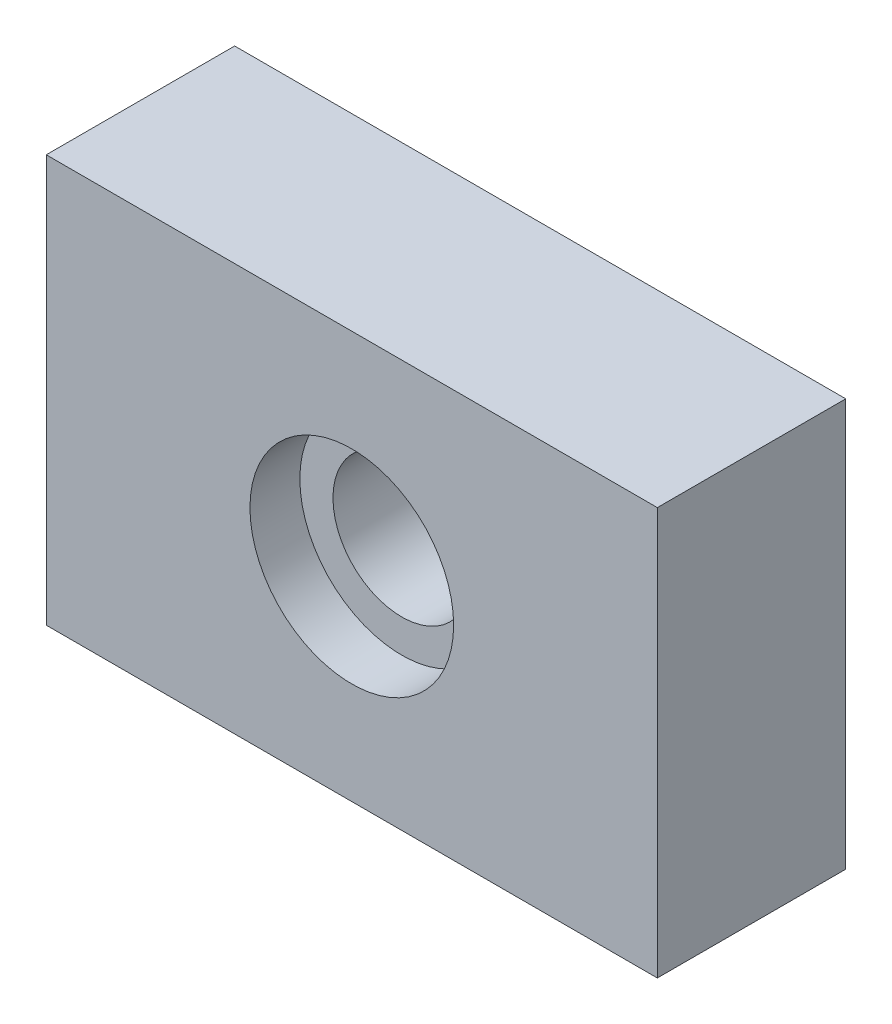
SolidWorks part; units mm, degrees
material "1060 Alloy"
ref_plane "Front Plane" through (0, 0, 0) normal (0, 0, 1) x (1, 0, 0)
ref_plane "Top Plane" through (0, 0, 0) normal (0, 1, 0) x (1, 0, 0)
ref_plane "Right Plane" through (0, 0, 0) normal (1, 0, 0) x (0, 0, -1)
sketch "Sketch1" plane through (0, 0, 0) normal (0, 0, 1) x (1, 0, 0)
  line L1 (0, 0) -> (152.4, 0)
  line L2 (0, 0) -> (0, 101.6)
  line L3 (0, 101.6) -> (152.4, 101.6)
  line L4 (152.4, 0) -> (152.4, 101.6)
  dimension "D1" = 152.4
  dimension "D2" = 101.6
extrude "Boss-Extrude1" add sketch "Sketch1" along normal blind 46.99
sketch "Sketch2" plane through (0, 0, 0) normal (0, 0, -1) x (-1, 0, 0)
  line L0 (0, 50.8) -> (-152.4, 50.8) construction
  line L1 (0, 101.6) -> (0, 0) construction
  line L2 (-152.4, 0) -> (-152.4, 101.6) construction
  line L4 (-152.4, 101.6) -> (0, 101.6) construction
  line L5 (-76.2, 101.6) -> (-76.2, 0) construction
  line L6 (0, 0) -> (-152.4, 0) construction
  circle A0 centre (-76.2, 50.8) radius 25.4
  circle A1 centre (-76.2, 50.8) radius 17.145
  dimension "D1" = 50.8
  dimension "D2" = 34.29
extrude "Cut-Extrude1" cut sketch "Sketch2" against normal through all contours A1
extrude "Cut-Extrude3" cut sketch "Sketch2<2>" against normal blind 12.446
sketch "Sketch2<2>" plane through (0, 0, 0) normal (0, 0, -1) x (-1, 0, 0) same geometry as "Sketch2"
ref_plane "Plane2" through (0, 0, 23.495) normal (0, 0, -1) x (-1, 0, 0)
mirror "Mirror2" about plane through (0, 0, 23.495) normal (0, 0, -1) of "Cut-Extrude3"
hole_wizard "Tap Drill for 1/2-13 Tap1" positions "Sketch4" profile "Sketch5" hole size "1/2-13" standard "ANSI Inch"
sketch "Sketch4" plane through (0, 0, 0) normal (0, -1, 0) x (-1, 0, 0)
  line L0 (55.88, -23.495) -> (-55.88, -23.495) construction
  line L2 (-76.2, -46.99) -> (-76.2, 0) construction
  line L3 (0, -46.99) -> (-152.4, -46.99) construction
  line L4 (0, 0) -> (-152.4, 0) construction
  point P0 (-66.6533, -23.495)
  point P4 (-28.5533, -23.495)
  dimension "D1" = 47.6467
  dimension "D2" = 38.1
sketch "Sketch5" plane through (66.6533, 0, 23.495) normal (1, 0, 0) x (0, 0, -1)
  line L0 (0, 0) -> (0, 20.9995)
  line L1 (0, 20.9995) -> (5.3581, 17.78)
  line L2 (5.3581, 17.78) -> (5.3581, 0)
  line L5 (5.3581, 0) -> (0, 0)
  line L10 (0, 20.9995) -> (-5.3581, 17.78) construction
  line L11 (0, -6.35) -> (0, 107.95) construction
  dimension "Hole Dia." = 10.7163
  dimension "Hole Depth" = 17.78
  dimension "Drill Angle" = 118
equation "\"through_diamiter\"= 1.35"
equation "\"D2@Sketch2\"= \"through_diamiter\""
equation "\"bearing depth\"= 0.5"
equation "\"hole spacing\" = 0.75"
equation "\"D1@Sketch4\" = \"hole spacing\"+\"center_distance\""
equation "\"center_distance\"= 1.125855"
